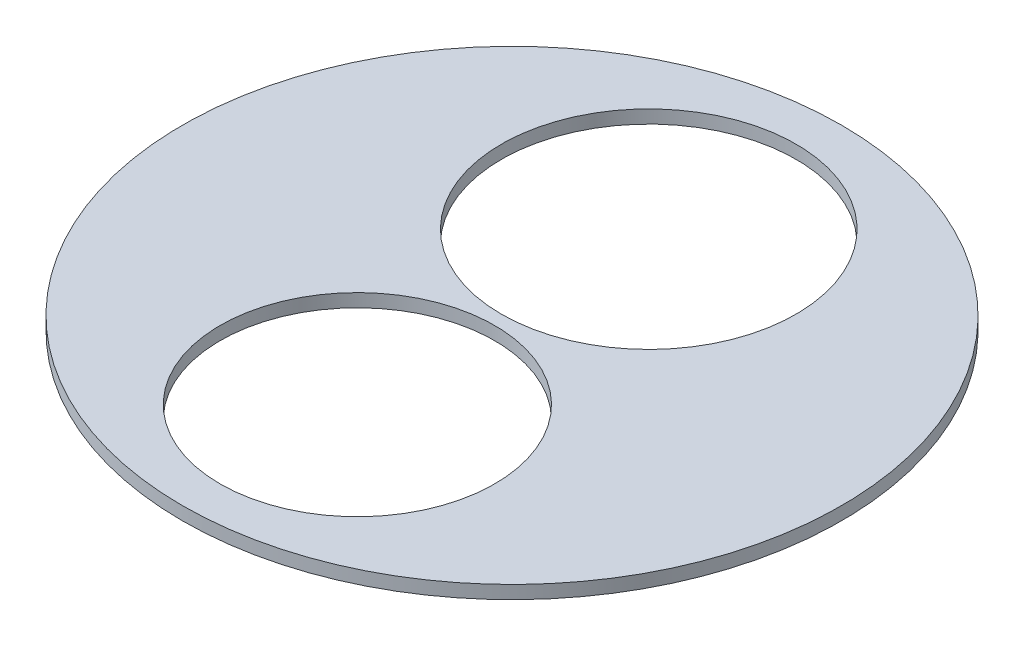
SolidWorks part; units mm, degrees
ref_plane "Front Plane" through (0, 0, 0) normal (0, 0, 1) x (1, 0, 0)
ref_plane "Top Plane" through (0, 0, 0) normal (0, 1, 0) x (1, 0, 0)
ref_plane "Right Plane" through (0, 0, 0) normal (1, 0, 0) x (0, 0, -1)
sketch "Sketch1" plane through (0, 0, 0) normal (0, 1, 0) x (1, 0, 0)
  circle A0 centre (0, 0) radius 1250
  circle A1 centre (-23.8911, 542.5713) radius 558.8
  circle A2 centre (0, -586.5136) radius 520.7
  point P5 (0, 657.7792)
  point P6 (0, -440.1858)
  point P7 (0, -453.5756)
  point P8 (0, -538.3778)
  point P9 (0, 577.4403)
  point P10 (0, -542.8411)
  point P13 (0, -542.8411)
  point P14 (0, 577.4403)
  point P15 (0, 0)
  point P16 (884.8595, 196.0866)
  point P17 (0, -597.3394)
  point P18 (0, 534.3105)
  point P19 (0, 0)
  point P20 (0, -586.5136)
  point P21 (-23.8911, 542.5713)
  dimension "D1" = 2500.0001
extrude "Boss-Extrude1" add sketch "Sketch1" along normal blind 50
